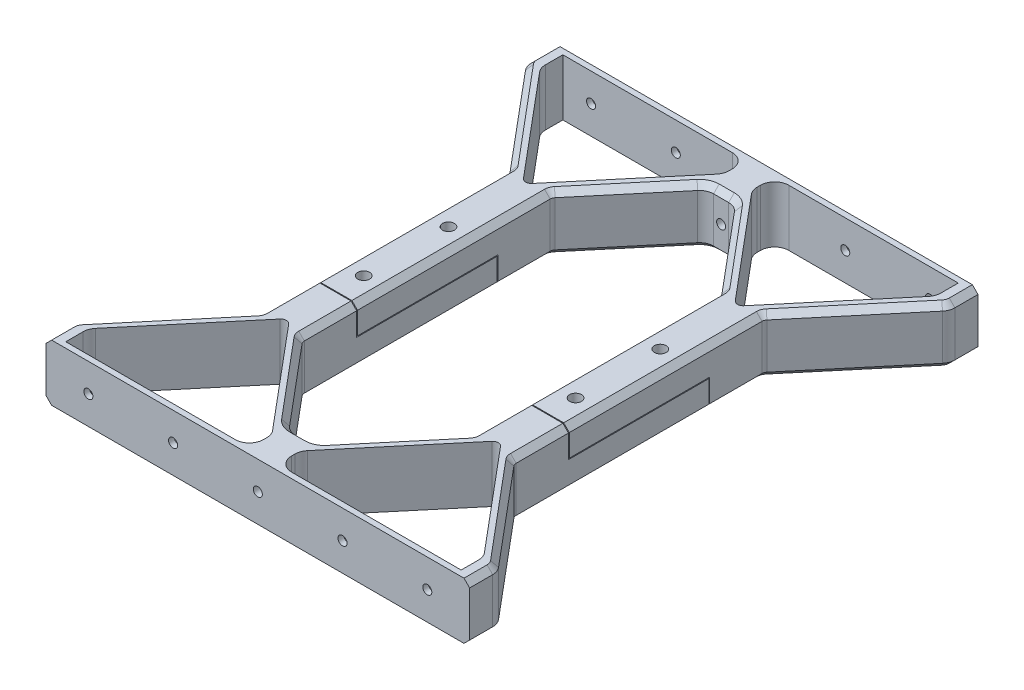
SolidWorks part; units mm, degrees
note: '?' marks a value the reader was unsure of.
ref_plane "Front Plane" through (0, 0, 0) normal (0, 0, 1) x (1, 0, 0)
ref_plane "Top Plane" through (0, 0, 0) normal (0, 1, 0) x (1, 0, 0)
ref_plane "Right Plane" through (0, 0, 0) normal (1, 0, 0) x (0, 0, -1)
ref_axis "X" through (-88.99, 0, 0) along (1, 0, 0)?
ref_axis "Y" through (0, 55, 0) along (0, -1, 0)?
ref_axis "Z" through (0, 0, -88.99) along (0, 0, 1)?
sketch "Sketch1" plane through (0, 0, 0) normal (0, 1, 0) x (1, 0, 0)
  line L0 (0, -90) -> (75, -90)
  line L1 (75, -90) -> (75, -80)
  line L2 (75, -80) -> (45, -44.2474)
  line L3 (70, -80) -> (37.5, -41.268)
  line L4 (45, -44.2474) -> (45, 0)
  line L5 (5, -88) -> (5, -80)
  line L6 (5, -80) -> (37.5, -41.268)
  line L7 (70, -80) -> (70, -88)
  line L8 (70, -88) -> (5, -88)
  line L9 (5, -74.0412) -> (30, -44.2474)
  line L10 (30, -44.2474) -> (30, 0)
  line L12 (0, 0) -> (30, 0) construction
  line L13 (30, 0) -> (45, 0)
  line L14 (37.5, -90) -> (37.5, -88) construction
  line L15 (37.5, -41.268) -> (37.5, 0) construction
  line L16 (70, -80) -> (75, -80) construction
  line L17 (0, 0) -> (0, -74.0412) construction
  line L18 (5, -74.0412) -> (0, -74.0412)
  line L19 (0, -74.0412) -> (0, -90)
  circle A0 centre (37.5, -15) radius 2.1
  dimension "D1" = 5
  dimension "D9" = 4.2
  dimension "D2" = 15
  dimension "D3" = 75
  dimension "D4" = 40
  dimension "D5" = 10
  dimension "D6" = 2
  dimension "D7" = 5
  dimension "D8" = 90
  dimension "D10" = 15
extrude "Boss-Extrude1" add sketch "Sketch1" along normal mid plane 20
fillet "Fillet1" radius 2 3 edges at (30, 0, 44.2474) (45, 0, 44.2474) (37.5, 0, 41.268)
fillet "Fillet2" radius 5 5 edges at (5, 0, 88) (75, 0, 80) (70, 0, 80) (5, 0, 74.0412) (5, 0, 80)
mirror "Mirror1" about plane through (0, 0, 0) normal (1, 0, 0) of bodies 101
sketch "Sketch3" plane through (0, 0, 0) normal (0, 0, 1) x (1, 0, 0)
  line L0 (0, 0) -> (-30, 0) construction
  line L1 (-30, 0) -> (-60, 0) construction
  line L2 (0, 0) -> (30, 0) construction
  line L3 (30, 0) -> (60, 0) construction
  circle A0 centre (0, 0) radius 1.6
  circle A1 centre (30, 0) radius 1.6
  circle A2 centre (60, 0) radius 1.6
  circle A3 centre (-30, 0) radius 1.6
  circle A4 centre (-60, 0) radius 1.6
  dimension "D1" = 3.2
  dimension "D2" = 30
extrude "Cut-Extrude1" cut sketch "Sketch3" against normal up to next from surface starting at face at (0, 0, 90)
mirror "Mirror2" about plane through (0, 0, 0) normal (0, 0, 1) of bodies 104 102
chamfer "Chamfer1" distance 2 angle 45 68 edges at (30, -10, 0) (-59.6491, -10, 61.7055) (-45, -10, 0) (-30, -10, 0) (-18.0154, -10, 58.5301) (-75, -10, 85.9099) (-75, 10, 85.9099) (-59.6491, 10, 61.7055) (-45, 10, 0) (-30, 10, 0) (-18.0154, 10, 58.5301) (-29.8794, 10, 44.2035) (-29.8794, -10, 44.2035) (-45.1206, 10, 44.2035) (-45.1206, -10, 44.2035) (-74.6985, 10, 80.1098) (-74.6985, -10, 80.1098) (-4.7816, 10, 73.5728) (-4.7816, -10, 73.5728) (75, -10, 85.9099) (-75, 10, -85.9099) (-74.6985, 10, -80.1098) (-59.6491, 10, -61.7055) (-45.1206, 10, -44.2035) (-29.8794, 10, -44.2035) (-18.0154, 10, -58.5301) (-4.7816, 10, -73.5728) (59.6491, -10, -61.7055) (18.0154, -10, -58.5301) (0, -10, -74.0412) (-4.7816, -10, -73.5728) (-29.8794, -10, -44.2035) (-45.1206, -10, -44.2035) (-74.6985, -10, -80.1098) (75, -10, -85.9099) (75, 10, -85.9099) (59.6491, 10, -61.7055) (18.0154, 10, -58.5301) (0, 10, -74.0412) (29.8794, 10, -44.2035) (29.8794, -10, -44.2035) (45.1206, 10, -44.2035) (45.1206, -10, -44.2035) (74.6985, 10, -80.1098) (74.6985, -10, -80.1098) (4.7816, 10, -73.5728) (4.7816, -10, -73.5728) (30, 10, 0) (-75, -10, -85.9099) (-59.6491, -10, -61.7055) (-18.0154, -10, -58.5301) (75, 10, 85.9099) (18.0154, -10, 58.5301) (18.0154, 10, 58.5301) (45, -10, 0) (45, 10, 0) (29.8794, -10, 44.2035) (29.8794, 10, 44.2035) (45.1206, -10, 44.2035) (45.1206, 10, 44.2035) (59.6491, -10, 61.7055) (59.6491, 10, 61.7055) (0, -10, 74.0412) (74.6985, -10, 80.1098) (0, 10, 74.0412) (74.6985, 10, 80.1098) (4.7816, -10, 73.5728) (4.7816, 10, 73.5728)
sketch "Sketch4" plane through (0, 0, 0) normal (1, 0, 0) x (0, 0, -1)
  line L0 (25, -0.15) -> (25, -10)
  line L1 (-25, 0.15) -> (25, 0.15)
  line L2 (-25, 0.15) -> (-25, -0.15)
  line L3 (-25, -0.15) -> (25, -0.15)
  line L4 (25, 0.15) -> (25, -0.15)
  line L5 (-25, 0.15) -> (25, -0.15) construction
  line L6 (-25, -0.15) -> (25, 0.15) construction
  line L7 (25, -10) -> (24.7, -10)
  line L8 (24.7, -10) -> (24.7, -0.15)
  line L9 (-25, 0.15) -> (-25, 10)
  line L10 (-25, 10) -> (-24.7, 10)
  line L11 (-24.7, 10) -> (-24.7, 0.15)
  line L13 (-90, -10) -> (-81.8199, -10) construction
  line L14 (46.0906, 10) -> (43.5195, 10) construction
  point P0 (0, 0)
  dimension "D1" = 0.3
  dimension "D2" = 50
  dimension "D3" = 0.3
extrude "Cut-Extrude2" cut sketch "Sketch4" against normal through all both and the other way through all contours L11 L10 L9 L1 | L4 L1 L2 L3 | L8 L7 L0 L3
